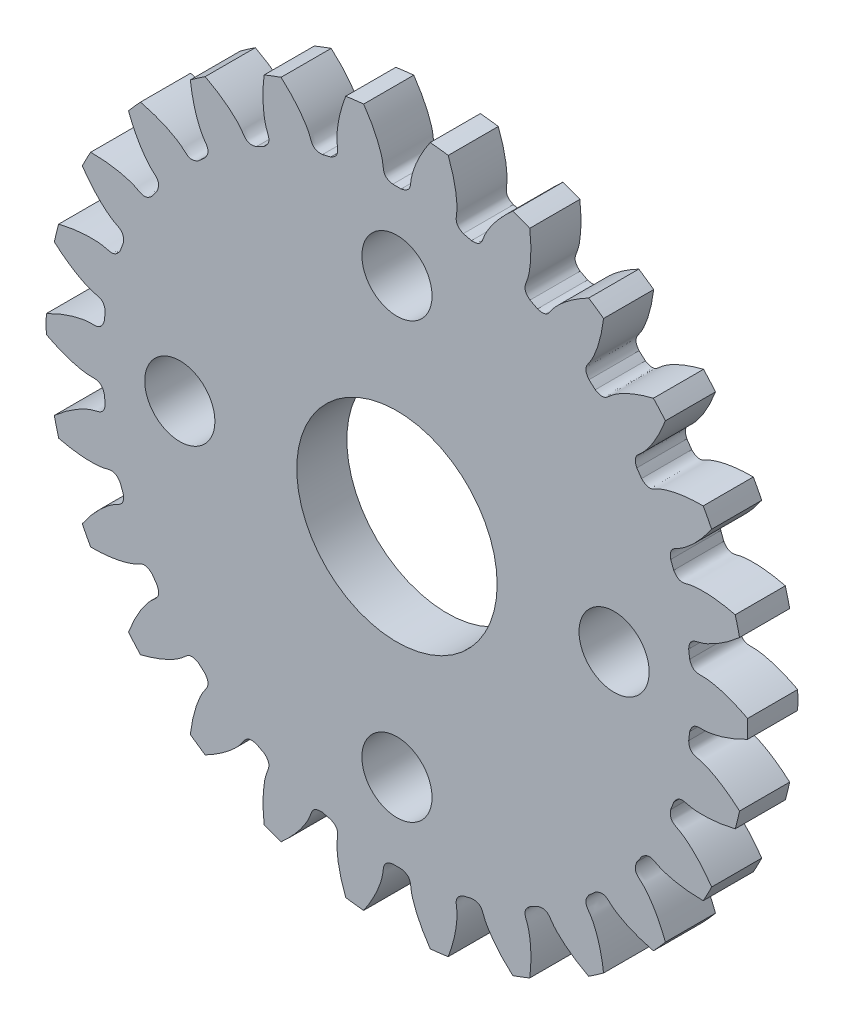
SolidWorks part; units mm, degrees
ref_plane "前视基准面" through (0, 0, 0) normal (0, 0, 1) x (1, 0, 0)
ref_plane "上视基准面" through (0, 0, 0) normal (0, 1, 0) x (1, 0, 0)
ref_plane "右视基准面" through (0, 0, 0) normal (1, 0, 0) x (0, 0, -1)
sketch "草图1" plane through (0, 0, 0) normal (0, 0, 1) x (1, 0, 0)
  circle A0 centre (0, 0) radius 21
extrude "凸台-拉伸1" add sketch "草图1" along normal blind 3
ref_axis "基准轴1" through (0, 0, -0.15) along (0, 0, 1)
sketch "草图2" plane through (0, 0, 0) normal (0, 0, 1) x (1, 0, 0)
  line L0 (0, 0) -> (0, 21) construction
  circle A0 centre (0, 0) radius 21 construction
  arc A1 (0.2506, 17.6232) -> (-0.2506, 17.6232) centre (0, 0) ccw
  arc A2 (4.9424, 23.9032) -> (-4.9424, 23.9032) centre (0, 0) ccw
  spline S0 degree 3 poles (0.2506, 17.6232) (0.8447, 17.7357) (0.7955, 18.0869) (0.8511, 18.4383) (0.8595, 18.4852) (0.8702, 18.5391) (0.8835, 18.6) (0.8998, 18.6677) (0.9193, 18.7421) (0.9423, 18.8232) (0.969, 18.9109) (0.9997, 19.0049) (1.0348, 19.1053) (1.0744, 19.2118) (1.1188, 19.3243) (1.1682, 19.4426) (1.223, 19.5667) (1.2833, 19.6962) (1.3495, 19.8312) (1.4217, 19.9713) (1.5001, 20.1163) (1.5851, 20.2662) (1.6767, 20.4206) (1.7754, 20.5794) (1.8811, 20.7423) (1.9942, 20.9092) (2.1149, 21.0797) (2.2433, 21.2537) (2.3796, 21.4309) (2.524, 21.6111) (2.6767, 21.7939) (2.8378, 21.9792) (3.0075, 22.1667) (3.186, 22.3561) (3.3733, 22.5471) (3.5696, 22.7394) (3.7751, 22.9329) (3.9899, 23.127) (4.214, 23.3217) (4.5293, 23.5846) (4.7745, 23.7768) (4.9424, 23.9032) knots 0 0 0 0 0.122665 0.127715 0.133684 0.14057 0.148375 0.157098 0.166739 0.177298 0.188775 0.201171 0.214485 0.228717 0.243867 0.259935 0.276922 0.294827 0.31365 0.333391 0.35405 0.375628 0.398124 0.421538 0.44587 0.47112 0.497289 0.524375 0.55238 0.581303 0.611145 0.641904 0.673582 0.706178 0.739692 0.774124 0.809475 0.845743 0.88293 0.921035 1 1 1 1
  spline S1 degree 3 poles (-0.2506, 17.6232) (-0.8447, 17.7357) (-0.7955, 18.0869) (-0.8511, 18.4383) (-0.8595, 18.4852) (-0.8702, 18.5391) (-0.8835, 18.6) (-0.8998, 18.6677) (-0.9193, 18.7421) (-0.9423, 18.8232) (-0.969, 18.9109) (-0.9997, 19.0049) (-1.0348, 19.1053) (-1.0744, 19.2118) (-1.1188, 19.3243) (-1.1682, 19.4426) (-1.223, 19.5667) (-1.2833, 19.6962) (-1.3495, 19.8312) (-1.4217, 19.9713) (-1.5001, 20.1163) (-1.5851, 20.2662) (-1.6767, 20.4206) (-1.7754, 20.5794) (-1.8811, 20.7423) (-1.9942, 20.9092) (-2.1149, 21.0797) (-2.2433, 21.2537) (-2.3796, 21.4309) (-2.524, 21.6111) (-2.6767, 21.7939) (-2.8378, 21.9792) (-3.0075, 22.1667) (-3.186, 22.3561) (-3.3733, 22.5471) (-3.5696, 22.7394) (-3.7751, 22.9329) (-3.9899, 23.127) (-4.214, 23.3217) (-4.5293, 23.5846) (-4.7745, 23.7768) (-4.9424, 23.9032) knots 0 0 0 0 0.122665 0.127715 0.133684 0.14057 0.148375 0.157098 0.166739 0.177298 0.188775 0.201171 0.214485 0.228717 0.243867 0.259935 0.276922 0.294827 0.31365 0.333391 0.35405 0.375628 0.398124 0.421538 0.44587 0.47112 0.497289 0.524375 0.55238 0.581303 0.611145 0.641904 0.673582 0.706178 0.739692 0.774124 0.809475 0.845743 0.88293 0.921035 1 1 1 1
extrude "切除-拉伸1" cut sketch "草图2" along normal through all
pattern_circular "阵列(圆周)1" count 26 every 13.846 about axis through (0, 0, -0.15) along (0, 0, 1) of "切除-拉伸1"
sketch "草图3" plane through (0, 0, 0) normal (0, 0, 1) x (1, 0, 0)
  circle A0 centre (0, 0) radius 19.5 construction
  dimension "Dn" = 39
sketch "草图5" plane through (0, 0, 3) normal (0, 0, 1) x (1, 0, 0)
  circle A0 centre (0, 0) radius 13 construction
  circle A1 centre (0, 13) radius 2.1
  circle A2 centre (13, 0) radius 2.1
  circle A3 centre (0, -13) radius 2.1
  circle A4 centre (-13, 0) radius 2.1
  circle A5 centre (0, 0) radius 6
  dimension "D1" = 26
  dimension "D2" = 4.2
  dimension "D4" = 12
  dimension "D3" = 4
extrude "切除-拉伸2" cut sketch "草图5" against normal through all
